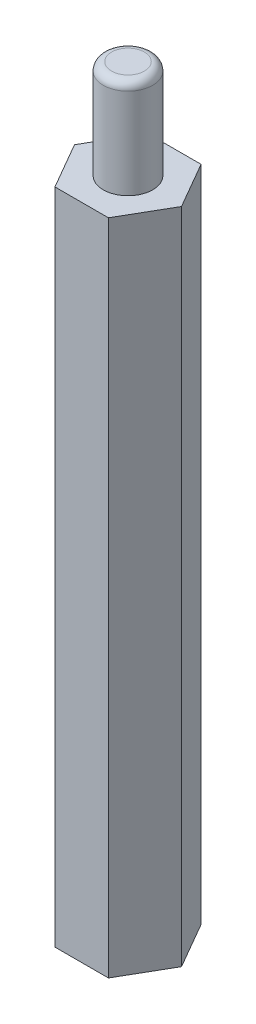
SolidWorks part; units mm, degrees
note: The reader was unsure of these and kept them because the rebuilt part matched: shared geometry of "草图1<2>".
ref_plane "前视基准面" through (0, 0, 0) normal (0, 0, 1) x (1, 0, 0)
ref_plane "上视基准面" through (0, 0, 0) normal (0, 1, 0) x (1, 0, 0)
ref_plane "右视基准面" through (0, 0, 0) normal (1, 0, 0) x (0, 0, -1)
sketch "草图1" plane through (0, 0, 0) normal (0, 1, 0) x (1, 0, 0)
  circle A0 centre (0, 0) radius 1.5
  dimension "D1" = 3
extrude "凸台-拉伸1" add sketch "草图1" along normal blind 46
fillet "圆角1" radius 0.5 1 edges at (0, 46, 1.5)
sketch "草图2" plane through (0, 0, 0) normal (0, 1, 0) x (1, 0, 0)
  line L1 (-1.625, 2.8146) -> (-3.25, 0)
  line L2 (-3.25, 0) -> (-1.625, -2.8146)
  line L3 (-1.625, -2.8146) -> (1.625, -2.8146)
  line L4 (1.625, -2.8146) -> (3.25, 0)
  line L5 (3.25, 0) -> (1.625, 2.8146)
  line L6 (1.625, 2.8146) -> (-1.625, 2.8146)
  circle A0 centre (0, 0) radius 3.25 construction
  circle A1 centre (0, 0) radius 1.5
  dimension "D1" = 3
  dimension "D2" = 6.5
extrude "凸台-拉伸2" add sketch "草图2" along normal blind 40
extrude "切除-拉伸1" cut sketch "草图1<2>" along normal blind 10
sketch "草图1<2>" plane through (0, 0, 0) normal (0, 1, 0) x (1, 0, 0) same geometry as "草图1"
